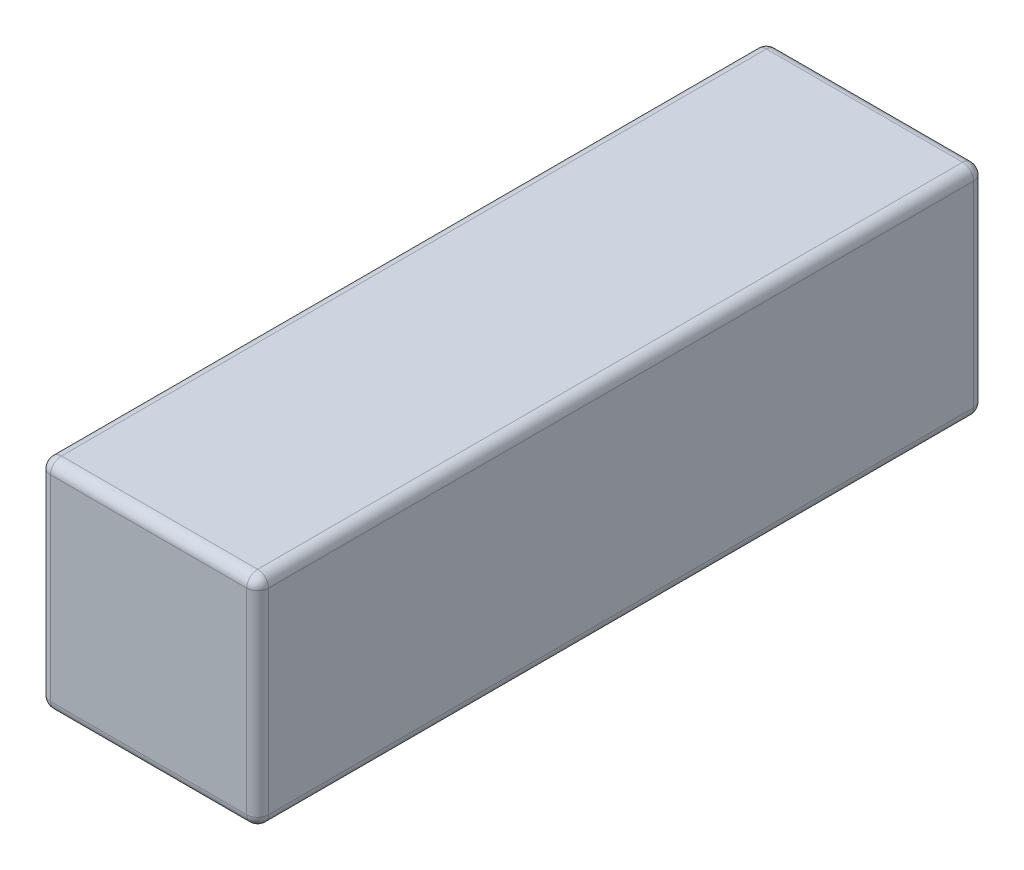
SolidWorks part; units mm, degrees
ref_plane "Front Plane" through (0, 0, 0) normal (0, 0, 1) x (1, 0, 0)
ref_plane "Top Plane" through (0, 0, 0) normal (0, 1, 0) x (1, 0, 0)
ref_plane "Right Plane" through (0, 0, 0) normal (1, 0, 0) x (0, 0, -1)
sketch "Sketch1" plane through (0, 0, 0) normal (0, 0, 1) x (1, 0, 0)
  line L3 (1.5, -1.5) -> (-1.5, -1.5)
  line L4 (1.5, -1.5) -> (1.5, 1.5)
  line L5 (1.5, 1.5) -> (-1.5, 1.5)
  line L6 (-1.5, -1.5) -> (-1.5, 1.5)
  line L7 (1.5, -1.5) -> (-1.5, 1.5) construction
  line L8 (1.5, 1.5) -> (-1.5, -1.5) construction
  point P0 (0, 0)
  dimension "Width" = 3
  dimension "Height" = 3
sketch "Sketch2" plane through (0, 0, 0) normal (1, 0, 0) x (0, 0, -1)
  line L2 (6, -1.5) -> (-6, -1.5)
  line L3 (6, -1.5) -> (6, 1.5)
  line L4 (6, 1.5) -> (-6, 1.5)
  line L5 (-6, -1.5) -> (-6, 1.5)
  line L6 (6, -1.5) -> (-6, 1.5) construction
  line L7 (6, 1.5) -> (-6, -1.5) construction
  point P0 (0, 0)
  point P4 (0, 0)
  dimension "Length" = 12
sketch "Sketch3" plane through (0, 0, 0) normal (0, 0, 1) x (1, 0, 0)
  line L0 (1.5, -1.5) -> (1.5, 1.5) construction
  line L5 (1.5, -1.5) -> (-1.5, -1.5) construction
  line L6 (-1.5, -1.5) -> (-1.5, 1.5) construction
  line L7 (1.5, 1.5) -> (-1.5, 1.5) construction
  line L8 (1.5, -1.5) -> (1.5, 1.5)
  line L9 (1.5, -1.5) -> (-1.5, -1.5)
  line L10 (-1.5, -1.5) -> (-1.5, 1.5)
  line L11 (1.5, 1.5) -> (-1.5, 1.5)
extrude "Boss-Extrude1" add sketch "Sketch3" along normal up to vertex (6 mm away) and the other way up to vertex (6 mm away) up to point (0, 1.5, 6) other way up to point (0, 1.5, -6)
fillet "Fillet2" radius 0.15 12 edges at (-1.5, 0, -6) (0, -1.5, -6) (-1.5, 1.5, 0) (0, 1.5, -6) (1.5, 1.5, 0) (1.5, 0, -6) (1.5, -1.5, 0) (-1.5, 0, 6) (0, 1.5, 6) (1.5, 0, 6) (0, -1.5, 6) (-1.5, -1.5, 0)
ref_plane "Contact Plane 1" through (0, 0, 6) normal (0, 0, 1) x (1, 0, 0)
ref_plane "Contact Plane 2" through (0, 0, -6) normal (0, 0, 1) x (1, 0, 0)
ref_axis "Center Axis 1" through (0, 0, -4.4) along (0, 0, 1)
sketch "Esquisse1" plane through (0, 0, 6) normal (0, 0, 1) x (1, 0, 0)
  line L0 (1.5, -1.35) -> (1.5, 1.35) construction
  line L1 (-1.5, -1.5) -> (1.5, -1.5)
  line L2 (-1.5, -1.5) -> (-1.5, 1.5)
  line L3 (-1.5, 1.5) -> (1.5, 1.5)
  line L4 (1.5, -1.5) -> (1.5, 1.5)
  line L5 (-1.5, -1.5) -> (1.5, 1.5) construction
  line L6 (-1.5, 1.5) -> (1.5, -1.5) construction
  line L7 (1.35, 1.5) -> (-1.35, 1.5) construction
  point P0 (0, 0)
extrude "Enlèv. mat.-Extru.1" cut sketch "Esquisse1" against normal blind 2
fillet "Congé1" radius 0.15 8 edges at (1.4561, 1.4561, 4) (1.5, 0, 4) (1.4561, -1.4561, 4) (0, -1.5, 4) (-1.4561, -1.4561, 4) (-1.5, 0, 4) (-1.4561, 1.4561, 4) (0, 1.5, 4)
